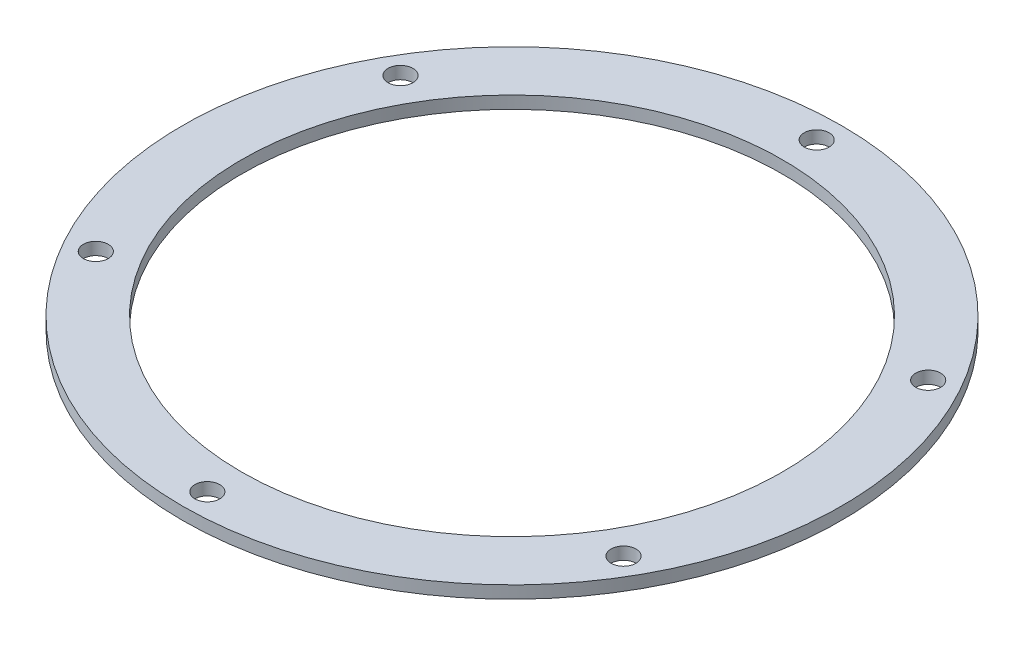
SolidWorks part; units mm, degrees
material "PLA"
ref_plane "Front Plane" through (0, 0, 0) normal (0, 0, 1) x (1, 0, 0)
ref_plane "Top Plane" through (0, 0, 0) normal (0, 1, 0) x (1, 0, 0)
ref_plane "Right Plane" through (0, 0, 0) normal (1, 0, 0) x (0, 0, -1)
sketch "Sketch1" plane through (0, 0, 0) normal (0, 1, 0) x (1, 0, 0)
  circle A0 centre (0, 0) radius 53
  circle A1 centre (0, 0) radius 43.5
  circle A2 centre (0, 0) radius 49 construction
  circle A3 centre (0, 49) radius 2
  circle A4 centre (42.4352, 24.5) radius 2
  circle A5 centre (42.4352, -24.5) radius 2
  circle A6 centre (0, -49) radius 2
  circle A7 centre (-42.4352, -24.5) radius 2
  circle A8 centre (-42.4352, 24.5) radius 2
  point P19 (0, 0)
  dimension "D1" = 106
  dimension "D2" = 87
  dimension "D3" = 98
  dimension "D4" = 4
  dimension "D5" = 6
extrude "Boss-Extrude1" add sketch "Sketch1" along normal blind 2
equation "\"Np_b\" = 40"
equation "\"Np_s\" = 28"
equation "\"Nr_b\" = 128"
equation "\"Nr_s\" = 116"
equation "\"Ns\" = 48"
equation "\"Motor_case_ID\" = 116.8"
equation "\"Motor_case_OD_base_to_chamfer\" = 5"
equation "\"Motor_case_OD_max\" = 131.3"
equation "\"Motor_case_thickness\" = 2.5"
equation "\"air_flow_hole_offset\" = 3"
equation "\"standard_bearing_insertion_chamfer\" = 0.5"
equation "\"alpha_p_b\" = 0.8539582918412485"
equation "\"alpha_p_s\" = 0.8539582918412592"
equation "\"alpha_r_b\" = 0.8539582918412556"
equation "\"alpha_r_s\" = 0.8539582918412556"
equation "\"alpha_s\" = 0.8539582918412343"
equation "\"base_plate_thickness\" = 4"
equation "\"bearing_ID\" = 70"
equation "\"bearing_OD\" = 90"
equation "\"bearing_height\" = 10"
equation "\"bearing mount thickness\" = 8"
equation "\"bearing_retainer_thickness\" = 2"
equation "\"beta_p_b\" = 2.792083416317503"
equation "\"beta_p_s\" = 4.7206548448889105"
equation "\"beta_r_b\" = 3.114166583682511"
equation "\"beta_r_s\" = 3.259640721613546"
equation "\"beta_s\" = 2.0420834163175314"
equation "\"carrier_PCD\" = 61.599999999999994"
equation "\"carrier_bearing_step_width\" = 1.5"
equation "\"carrier_small_ring_inner_bearing_ID\" = 20"
equation "\"carrier_small_ring_inner_bearing_OD\" = 32"
equation "\"carrier_small_ring_inner_bearing_flap\" = 2"
equation "\"carrier_small_ring_inner_bearing_height\" = 7"
equation "\"carrier_thickness\" = 4"
equation "\"carrier_trapezoidal_support_hole_PCD_offset_bearing_ID\" = 4"
equation "\"carrier_trapezoidal_support_hole_dia\" = 3"
equation "\"carrier_trapezoidal_support_hole_socket_head_dia\" = 5.5"
equation "\"carrier_trapezoidal_support_hole_wrench_size\" = 5.5"
equation "\"carrier_trapezoidal_support_sun_offset\" = 5"
equation "\"case_dist\" = 6.5"
equation "\"case_mounting_PCD\" = 123.8"
equation "\"case_mounting_bolt_depth\" = 4.5"
equation "\"case_mounting_hole_allen_socket_dia\" = 5.5"
equation "\"case_mounting_hole_dia\" = 3"
equation "\"case_mounting_hole_shift\" = 1.0"
equation "\"case_mounting_nut_clearance\" = 2"
equation "\"case_mounting_nut_thickness\" = 2.4"
equation "\"case_mounting_surface_height\" = 4"
equation "\"case_mounting_wrench_size\" = 5.5"
equation "\"central_hole_offset_from_motor_mount_PCD\" = 5"
equation "\"clearance_case_mount_holes_shell_thickness\" = 1"
equation "\"clearance_motor_and_case\" = 5"
equation "\"clearance_planet\" = 1.5"
equation "\"clearance_sun_coupler_sec_carrier\" = 1.5"
equation "\"clr_tip_root\" = 0.17500000000000004"
equation "\"clr_tip_root_s\" = 0.17500000000000004"
equation "\"db_p_b\" = 26.311393382005434"
equation "\"db_p_s\" = 18.417975367403802"
equation "\"db_r_b\" = 84.19645882241738"
equation "\"db_r_s\" = 76.30304080781575"
equation "\"db_s\" = 31.57367205840652"
equation "\"dp_p_b\" = 28.0"
equation "\"dp_p_s\" = 19.599999999999998"
equation "\"dp_r_b\" = 89.6"
equation "\"dp_r_s\" = 81.19999999999999"
equation "\"dp_s\" = 33.599999999999994"
equation "\"driver_lower_holes_dist_from_center\" = 13"
equation "\"driver_mount_height\" = 6"
equation "\"driver_mount_holes_dia\" = 3"
equation "\"driver_mount_inserts_OD\" = 4.8"
equation "\"driver_mount_thickness\" = 1.5"
equation "\"driver_side_holes_dist_from_center\" = 22.5"
equation "\"driver_upper_holes_dist_from_center\" = 29"
equation "\"fw_p_b\" = 29.99577312706301"
equation "\"fw_p_s\" = 25.912913082891553"
equation "\"fw_r_b\" = 29.99577312706301"
equation "\"fw_r_s\" = 24.412913082891553"
equation "\"fw_s_calc\" = 5.685933367726717"
equation "\"fw_s_used\" = 63.40868620995457"
equation "\"gear_casing_big_ring_to_bearing_dist\" = 34.91291308289155"
equation "\"gear_casing_thickness\" = 4"
equation "\"h_a\" = 0.7"
equation "\"h_b\" = 0.875"
equation "\"h_f\" = 0.875"
equation "\"module\" = 0.7"
equation "\"motor_OD\" = 106.8"
equation "\"motor_case_OD_base\" = 121.8"
equation "\"motor_height\" = 47.6"
equation "\"motor_mount_hole_PCD\" = 40"
equation "\"motor_mount_hole_dia\" = 5"
equation "\"motor_mount_hole_num\" = 4"
equation "\"motor_output_hole_CSK_OD\" = 8"
equation "\"motor_output_hole_CSK_head_height\" = 2.0"
equation "\"motor_output_hole_PCD\" = 23"
equation "\"motor_output_hole_dia\" = 4"
equation "\"motor_output_hole_num\" = 4"
equation "\"num_planet\" = 4"
equation "\"output_mounting_PCD\" = 98"
equation "\"output_mounting_hole_dia\" = 4"
equation "\"output_mounting_nut_depth\" = 3"
equation "\"output_mounting_nut_thickness\" = 3.2"
equation "\"output_mounting_nut_wrench_size\" = 7"
equation "\"pattern_bulge_dia\" = 3"
equation "\"pattern_depth\" = 2"
equation "\"pattern_num_bulge\" = 18"
equation "\"pattern_offset_from_motor_case_OD_base\" = 3"
equation "\"planet_bearing_OD\" = 12"
equation "\"planet_bearing_width\" = 3.5"
equation "\"planet_bore\" = 10"
equation "\"planet_pin_bolt_dia\" = 5"
equation "\"planet_pin_bolt_wrench_size\" = 8"
equation "\"planet_pin_socket_head_dia\" = 8.5"
equation "\"planet_shaft_dia\" = 8"
equation "\"planet_shaft_step_offset\" = 1"
equation "\"pressure_angle\" = 20.0"
equation "\"pressure angle\" = 20.0"
equation "\"ring_OD_b\" = 99.6"
equation "\"ring_radial_thickness\" = 5"
equation "\"ring_to_chamfer_clearance\" = 1.5"
equation "\"sec_carrier_thickness\" = 5"
equation "\"small_ring_case_thickness\" = 4"
equation "\"small_ring_output_wall_thickness\" = 5"
equation "\"small_ring_output_wall_to_bearing_shaft_attachement_hole_CSK_OD\" = 8"
equation "\"small_ring_output_wall_to_bearing_shaft_attachement_hole_CSK_head_height\" = 2.0"
equation "\"small_ring_output_wall_to_bearing_shaft_attachement_hole_depth\" = 6.5"
equation "\"small_ring_output_wall_to_bearing_shaft_attachement_hole_dia\" = 4"
equation "\"small_ring_output_wall_to_bearing_shaft_attachement_hole_num\" = 3"
equation "\"small_ring_output_wall_to_bearing_shaft_attachement_hole_pcd\" = 12"
equation "\"small_ring_output_wall_to_bearing_shaft_attachement_nut_thickness\" = 3.2"
equation "\"small_ring_output_wall_to_bearing_shaft_attachement_nut_wrench\" = 7"
equation "\"standard_clearance_1_5mm\" = 1.5"
equation "\"standard_fillet_1_5mm\" = 1.5"
equation "\"sun_central_bolt_dia\" = 5"
equation "\"sun_central_bolt_socket_head_dia\" = 8.5"
equation "\"sun_coupler_hub_thickness\" = 4"
equation "\"sun_hub_dia\" = 30.0"
equation "\"sun_shaft_bearing_ID\" = 8"
equation "\"sun_shaft_bearing_OD\" = 16"
equation "\"sun_shaft_bearing_width\" = 5"
equation "\"wire_slot_dist_from_center\" = 45.5"
equation "\"wire_slot_length\" = 10"
equation "\"wire_slot_radius\" = 3"
equation "\"tight_clearance_3DP\" = 0.4"
equation "\"loose_clearance_3DP\" = 0.8"
equation "\"D1@Sketch1\"= \"bearing_OD\" + \"bearing mount thickness\" * 2"
equation "\"D2@Sketch1\"=\"bearing_OD\" -  \"standard_clearance_1_5mm\"*2"
equation "\"D3@Sketch1\"= \"output_mounting_PCD\""
equation "\"D4@Sketch1\"= \"output_mounting_hole_dia\""
equation "\"D1@Boss-Extrude1\"= \"bearing_retainer_thickness\""
